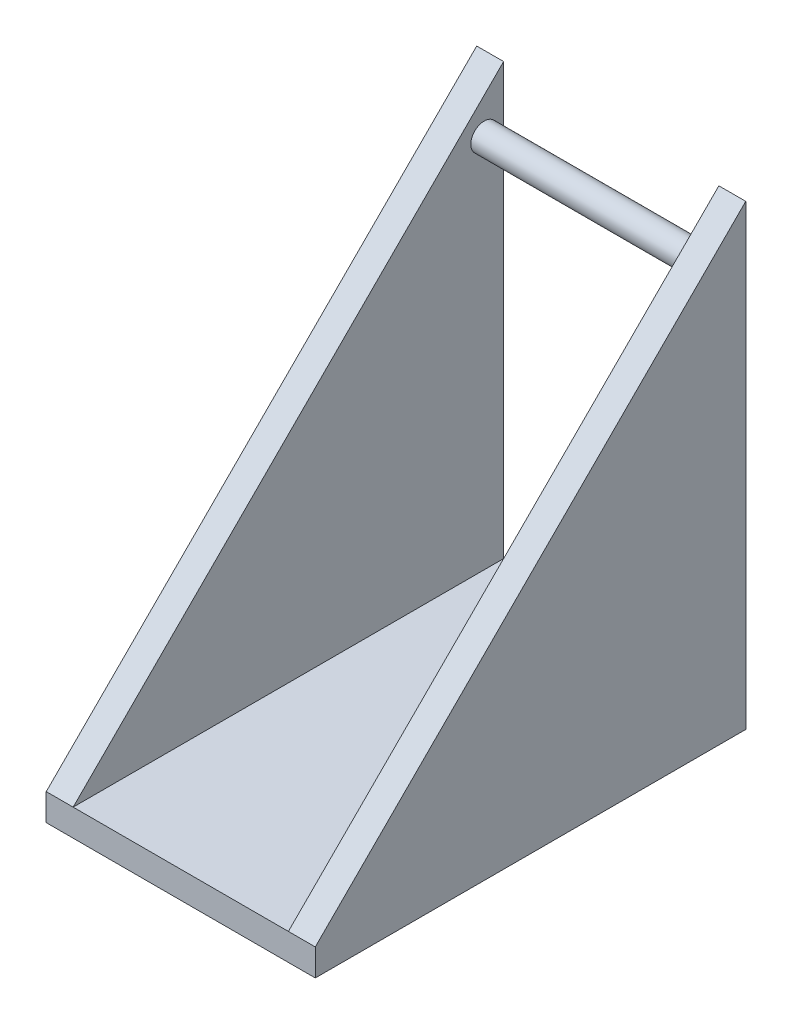
SolidWorks part; units mm, degrees
material "Plain Carbon Steel"
ref_plane "Front Plane" through (0, 0, 0) normal (0, 0, 1) x (1, 0, 0)
ref_plane "Top Plane" through (0, 0, 0) normal (0, 1, 0) x (1, 0, 0)
ref_plane "Right Plane" through (0, 0, 0) normal (1, 0, 0) x (0, 0, -1)
sketch "Sketch2" plane through (0, 0, 0) normal (0, 0, 1) x (1, 0, 0)
  line L1 (0, 0) -> (63.5, 0)
  line L2 (0, 0) -> (0, 6.35)
  line L3 (0, 6.35) -> (63.5, 6.35)
  line L4 (63.5, 0) -> (63.5, 6.35)
  dimension "D1" = 6.35
  dimension "D2" = 63.5
extrude "Base" add sketch "Sketch2" along normal blind 101.6
ref_plane "Plane1" through (31.75, 0, 0) normal (-1, 0, 0) x (0, 0, 1)
sketch "Sketch4" plane through (63.5, 0, 0) normal (1, 0, 0) x (0, 0, -1)
  line L0 (0, 107.95) -> (0, 6.35)
  line L2 (0, 6.35) -> (-101.6, 6.35)
  line L3 (-101.6, 6.35) -> (0, 6.35) construction
  line L4 (-101.6, 6.35) -> (0, 107.95)
  line L5 (-101.6, 0) -> (-101.6, 6.35) construction
extrude "Rib" add sketch "Sketch4" against normal blind 6.35
mirror "RibCopy" about plane through (31.75, 0, 0) normal (-1, 0, 0) of "Rib"
sketch "Sketch5" plane through (57.15, 0, 0) normal (-1, 0, 0) x (0, 0, 1)
  circle A0 centre (4.5744, 94.9056) radius 3.175
  dimension "D1" = 6.35
extrude "Boss-Extrude4" add sketch "Sketch5" along normal up to next
